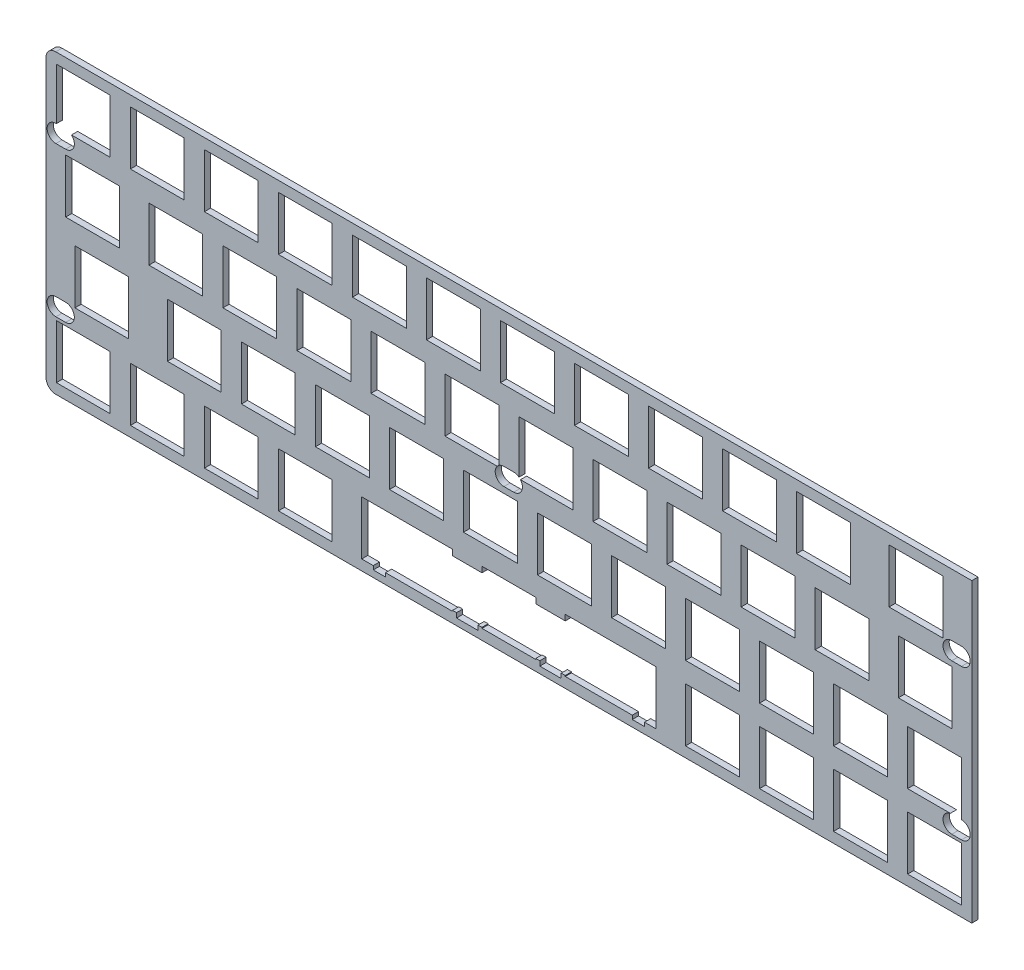
SolidWorks part; units mm, degrees
ref_plane "Front Plane" through (0, 0, 0) normal (0, 0, 1) x (1, 0, 0)
ref_plane "Top Plane" through (0, 0, 0) normal (0, 1, 0) x (1, 0, 0)
ref_plane "Right Plane" through (0, 0, 0) normal (1, 0, 0) x (0, 0, -1)
sketch "Model" plane through (0, 0, 0) normal (0, 0, 1) x (1, 0, 0)
  line L0 (0.0951, 76.4575) -> (238.37, 76.4575)
  line L1 (238.37, 76.4575) -> (238.37, 0.1075)
  line L2 (238.37, 0.1075) -> (0.0951, 0.1075)
  line L3 (0.0951, 0.1075) -> (0.0951, 76.4575)
  line L4 (81.3513, 16.6329) -> (81.3513, 2.7836)
  line L5 (81.3513, 2.7836) -> (84.3248, 2.7836)
  line L6 (84.3248, 2.7836) -> (84.3248, 1.8135)
  line L7 (84.3248, 1.8135) -> (87.4751, 1.8135)
  line L8 (87.4751, 1.8135) -> (87.4751, 2.7836)
  line L9 (87.4751, 2.7836) -> (104.725, 2.7836)
  line L10 (104.725, 2.7836) -> (104.725, 3.0138)
  line L11 (104.725, 3.0138) -> (105.756, 3.0138)
  line L12 (105.756, 3.0138) -> (105.756, 1.8135)
  line L13 (105.756, 1.8135) -> (111.275, 1.8135)
  line L14 (111.275, 1.8135) -> (111.275, 3.0138)
  line L15 (111.275, 3.0138) -> (112.306, 3.0138)
  line L16 (112.306, 3.0138) -> (112.306, 2.7836)
  line L17 (112.306, 2.7836) -> (126.157, 2.7836)
  line L18 (126.157, 2.7836) -> (126.157, 3.0138)
  line L19 (126.157, 3.0138) -> (127.187, 3.0138)
  line L20 (127.187, 3.0138) -> (127.187, 1.8135)
  line L21 (127.187, 1.8135) -> (132.707, 1.8135)
  line L22 (132.707, 1.8135) -> (132.707, 3.0138)
  line L23 (132.707, 3.0138) -> (133.737, 3.0138)
  line L24 (133.737, 3.0138) -> (133.737, 2.7836)
  line L25 (133.737, 2.7836) -> (150.987, 2.7836)
  line L26 (150.987, 2.7836) -> (150.987, 1.8135)
  line L27 (150.987, 1.8135) -> (154.138, 1.8135)
  line L28 (154.138, 1.8135) -> (154.138, 2.7836)
  line L29 (154.138, 2.7836) -> (157.113, 2.7836)
  line L30 (157.113, 2.7836) -> (157.113, 16.6329)
  line L31 (157.113, 16.6329) -> (133.737, 16.6329)
  line L32 (133.737, 16.6329) -> (133.737, 15.1639)
  line L33 (133.737, 15.1639) -> (126.157, 15.1639)
  line L34 (126.157, 15.1639) -> (126.157, 16.6329)
  line L35 (126.157, 16.6329) -> (112.306, 16.6329)
  line L36 (112.306, 16.6329) -> (112.306, 15.1639)
  line L37 (112.306, 15.1639) -> (104.725, 15.1639)
  line L38 (104.725, 15.1639) -> (104.725, 16.6329)
  line L39 (104.725, 16.6329) -> (81.3513, 16.6329)
  line L40 (221.845, 16.6329) -> (235.694, 16.6329)
  line L41 (235.694, 16.6329) -> (235.694, 2.7836)
  line L42 (235.694, 2.7836) -> (221.845, 2.7836)
  line L43 (221.845, 2.7836) -> (221.845, 16.6329)
  line L44 (202.795, 16.6329) -> (216.644, 16.6329)
  line L45 (216.644, 16.6329) -> (216.644, 2.7836)
  line L46 (216.644, 2.7836) -> (202.795, 2.7836)
  line L47 (202.795, 2.7836) -> (202.795, 16.6329)
  line L48 (183.745, 16.6329) -> (197.594, 16.6329)
  line L49 (197.594, 16.6329) -> (197.594, 2.7836)
  line L50 (197.594, 2.7836) -> (183.745, 2.7836)
  line L51 (183.745, 2.7836) -> (183.745, 16.6329)
  line L52 (164.695, 16.6329) -> (178.544, 16.6329)
  line L53 (178.544, 16.6329) -> (178.544, 2.7836)
  line L54 (178.544, 2.7836) -> (164.695, 2.7836)
  line L55 (164.695, 2.7836) -> (164.695, 16.6329)
  line L56 (59.92, 16.6329) -> (73.769, 16.6329)
  line L57 (73.769, 16.6329) -> (73.769, 2.7836)
  line L58 (73.769, 2.7836) -> (59.92, 2.7836)
  line L59 (59.92, 2.7836) -> (59.92, 16.6329)
  line L60 (40.87, 16.6329) -> (54.719, 16.6329)
  line L61 (54.719, 16.6329) -> (54.719, 2.7836)
  line L62 (54.719, 2.7836) -> (40.87, 2.7836)
  line L63 (40.87, 2.7836) -> (40.87, 16.6329)
  line L64 (21.8199, 16.6329) -> (35.669, 16.6329)
  line L65 (35.669, 16.6329) -> (35.669, 2.7836)
  line L66 (35.669, 2.7836) -> (21.8199, 2.7836)
  line L67 (21.8199, 2.7836) -> (21.8199, 16.6329)
  line L68 (2.7699, 16.6329) -> (16.6192, 16.6329)
  line L69 (16.6192, 16.6329) -> (16.6192, 2.7836)
  line L70 (16.6192, 2.7836) -> (2.7699, 2.7836)
  line L71 (2.7699, 2.7836) -> (2.7699, 16.6329)
  line L72 (221.845, 35.6828) -> (235.694, 35.6828)
  line L73 (235.694, 35.6828) -> (235.694, 21.8336)
  line L74 (235.694, 21.8336) -> (221.845, 21.8336)
  line L75 (221.845, 21.8336) -> (221.845, 35.6828)
  line L76 (202.795, 35.6828) -> (216.644, 35.6828)
  line L77 (216.644, 35.6828) -> (216.644, 21.8336)
  line L78 (216.644, 21.8336) -> (202.795, 21.8336)
  line L79 (202.795, 21.8336) -> (202.795, 35.6828)
  line L80 (183.745, 35.6828) -> (197.594, 35.6828)
  line L81 (197.594, 35.6828) -> (197.594, 21.8336)
  line L82 (197.594, 21.8336) -> (183.745, 21.8336)
  line L83 (183.745, 21.8336) -> (183.745, 35.6828)
  line L84 (164.695, 35.6828) -> (178.544, 35.6828)
  line L85 (178.544, 35.6828) -> (178.544, 21.8336)
  line L86 (178.544, 21.8336) -> (164.695, 21.8336)
  line L87 (164.695, 21.8336) -> (164.695, 35.6828)
  line L88 (145.644, 35.6828) -> (159.494, 35.6828)
  line L89 (159.494, 35.6828) -> (159.494, 21.8336)
  line L90 (159.494, 21.8336) -> (145.644, 21.8336)
  line L91 (145.644, 21.8336) -> (145.644, 35.6828)
  line L92 (126.594, 35.6828) -> (140.444, 35.6828)
  line L93 (140.444, 35.6828) -> (140.444, 21.8336)
  line L94 (140.444, 21.8336) -> (126.594, 21.8336)
  line L95 (126.594, 21.8336) -> (126.594, 35.6828)
  line L96 (107.544, 35.6828) -> (121.394, 35.6828)
  line L97 (121.394, 35.6828) -> (121.394, 21.8336)
  line L98 (121.394, 21.8336) -> (107.544, 21.8336)
  line L99 (107.544, 21.8336) -> (107.544, 35.6828)
  line L100 (88.4936, 35.6828) -> (102.344, 35.6828)
  line L101 (102.344, 35.6828) -> (102.344, 21.8336)
  line L102 (102.344, 21.8336) -> (88.4936, 21.8336)
  line L103 (88.4936, 21.8336) -> (88.4936, 35.6828)
  line L104 (69.445, 35.6828) -> (83.294, 35.6828)
  line L105 (83.294, 35.6828) -> (83.294, 21.8336)
  line L106 (83.294, 21.8336) -> (69.445, 21.8336)
  line L107 (69.445, 21.8336) -> (69.445, 35.6828)
  line L108 (50.395, 35.6828) -> (64.244, 35.6828)
  line L109 (64.244, 35.6828) -> (64.244, 21.8336)
  line L110 (64.244, 21.8336) -> (50.395, 21.8336)
  line L111 (50.395, 21.8336) -> (50.395, 35.6828)
  line L112 (31.3449, 35.6828) -> (45.194, 35.6828)
  line L113 (45.194, 35.6828) -> (45.194, 21.8336)
  line L114 (45.194, 21.8336) -> (31.3449, 21.8336)
  line L115 (31.3449, 21.8336) -> (31.3449, 35.6828)
  line L116 (7.531, 35.6828) -> (21.3817, 35.6828)
  line L117 (21.3817, 35.6828) -> (21.3817, 21.8336)
  line L118 (21.3817, 21.8336) -> (7.531, 21.8336)
  line L119 (7.531, 21.8336) -> (7.531, 35.6828)
  line L120 (219.462, 54.7328) -> (233.313, 54.7328)
  line L121 (233.313, 54.7328) -> (233.313, 40.8838)
  line L122 (233.313, 40.8838) -> (219.462, 40.8838)
  line L123 (219.462, 40.8838) -> (219.462, 54.7328)
  line L124 (198.031, 54.7328) -> (211.882, 54.7328)
  line L125 (211.882, 54.7328) -> (211.882, 40.8838)
  line L126 (211.882, 40.8838) -> (198.031, 40.8838)
  line L127 (198.031, 40.8838) -> (198.031, 54.7328)
  line L128 (178.981, 54.7328) -> (192.832, 54.7328)
  line L129 (192.832, 54.7328) -> (192.832, 40.8838)
  line L130 (192.832, 40.8838) -> (178.981, 40.8838)
  line L131 (178.981, 40.8838) -> (178.981, 54.7328)
  line L132 (159.931, 54.7328) -> (173.782, 54.7328)
  line L133 (173.782, 54.7328) -> (173.782, 40.8838)
  line L134 (173.782, 40.8838) -> (159.931, 40.8838)
  line L135 (159.931, 40.8838) -> (159.931, 54.7328)
  line L136 (140.881, 54.7328) -> (154.732, 54.7328)
  line L137 (154.732, 54.7328) -> (154.732, 40.8838)
  line L138 (154.732, 40.8838) -> (140.881, 40.8838)
  line L139 (140.881, 40.8838) -> (140.881, 54.7328)
  line L140 (121.831, 54.7328) -> (135.682, 54.7328)
  line L141 (135.682, 54.7328) -> (135.682, 40.8838)
  line L142 (135.682, 40.8838) -> (121.831, 40.8838)
  line L143 (121.831, 40.8838) -> (121.831, 54.7328)
  line L144 (102.781, 54.7328) -> (116.632, 54.7328)
  line L145 (116.632, 54.7328) -> (116.632, 40.8838)
  line L146 (116.632, 40.8838) -> (102.781, 40.8838)
  line L147 (102.781, 40.8838) -> (102.781, 54.7328)
  line L148 (83.7311, 54.7328) -> (97.5815, 54.7328)
  line L149 (97.5815, 54.7328) -> (97.5815, 40.8838)
  line L150 (97.5815, 40.8838) -> (83.7311, 40.8838)
  line L151 (83.7311, 40.8838) -> (83.7311, 54.7328)
  line L152 (64.6811, 54.7328) -> (78.5315, 54.7328)
  line L153 (78.5315, 54.7328) -> (78.5315, 40.8838)
  line L154 (78.5315, 40.8838) -> (64.6811, 40.8838)
  line L155 (64.6811, 40.8838) -> (64.6811, 54.7328)
  line L156 (45.6311, 54.7328) -> (59.4815, 54.7328)
  line L157 (59.4815, 54.7328) -> (59.4815, 40.8838)
  line L158 (59.4815, 40.8838) -> (45.6311, 40.8838)
  line L159 (45.6311, 40.8838) -> (45.6311, 54.7328)
  line L160 (26.581, 54.7328) -> (40.4315, 54.7328)
  line L161 (40.4315, 54.7328) -> (40.4315, 40.8838)
  line L162 (40.4315, 40.8838) -> (26.581, 40.8838)
  line L163 (26.581, 40.8838) -> (26.581, 54.7328)
  line L164 (5.1511, 54.7328) -> (19.0004, 54.7328)
  line L165 (19.0004, 54.7328) -> (19.0004, 40.8838)
  line L166 (19.0004, 40.8838) -> (5.1511, 40.8838)
  line L167 (5.1511, 40.8838) -> (5.1511, 54.7328)
  line L168 (217.081, 73.7828) -> (230.932, 73.7828)
  line L169 (230.932, 73.7828) -> (230.932, 59.9338)
  line L170 (230.932, 59.9338) -> (217.081, 59.9338)
  line L171 (217.081, 59.9338) -> (217.081, 73.7828)
  line L172 (193.27, 73.7828) -> (207.119, 73.7828)
  line L173 (207.119, 73.7828) -> (207.119, 59.9338)
  line L174 (207.119, 59.9338) -> (193.27, 59.9338)
  line L175 (193.27, 59.9338) -> (193.27, 73.7828)
  line L176 (174.22, 73.7828) -> (188.069, 73.7828)
  line L177 (188.069, 73.7828) -> (188.069, 59.9338)
  line L178 (188.069, 59.9338) -> (174.22, 59.9338)
  line L179 (174.22, 59.9338) -> (174.22, 73.7828)
  line L180 (155.17, 73.7828) -> (169.019, 73.7828)
  line L181 (169.019, 73.7828) -> (169.019, 59.9338)
  line L182 (169.019, 59.9338) -> (155.17, 59.9338)
  line L183 (155.17, 59.9338) -> (155.17, 73.7828)
  line L184 (136.12, 73.7828) -> (149.969, 73.7828)
  line L185 (149.969, 73.7828) -> (149.969, 59.9338)
  line L186 (149.969, 59.9338) -> (136.12, 59.9338)
  line L187 (136.12, 59.9338) -> (136.12, 73.7828)
  line L188 (117.07, 73.7828) -> (130.919, 73.7828)
  line L189 (130.919, 73.7828) -> (130.919, 59.9338)
  line L190 (130.919, 59.9338) -> (117.07, 59.9338)
  line L191 (117.07, 59.9338) -> (117.07, 73.7828)
  line L192 (98.02, 73.7828) -> (111.869, 73.7828)
  line L193 (111.869, 73.7828) -> (111.869, 59.9338)
  line L194 (111.869, 59.9338) -> (98.02, 59.9338)
  line L195 (98.02, 59.9338) -> (98.02, 73.7828)
  line L196 (78.97, 73.7828) -> (92.819, 73.7828)
  line L197 (92.819, 73.7828) -> (92.819, 59.9338)
  line L198 (92.819, 59.9338) -> (78.97, 59.9338)
  line L199 (78.97, 59.9338) -> (78.97, 73.7828)
  line L200 (59.92, 73.7828) -> (73.769, 73.7828)
  line L201 (73.769, 73.7828) -> (73.769, 59.9338)
  line L202 (73.769, 59.9338) -> (59.92, 59.9338)
  line L203 (59.92, 59.9338) -> (59.92, 73.7828)
  line L204 (40.87, 73.7828) -> (54.719, 73.7828)
  line L205 (54.719, 73.7828) -> (54.719, 59.9338)
  line L206 (54.719, 59.9338) -> (40.87, 59.9338)
  line L207 (40.87, 59.9338) -> (40.87, 73.7828)
  line L208 (21.8199, 73.7828) -> (35.669, 73.7828)
  line L209 (35.669, 73.7828) -> (35.669, 59.9338)
  line L210 (35.669, 59.9338) -> (21.8199, 59.9338)
  line L211 (21.8199, 59.9338) -> (21.8199, 73.7828)
  line L212 (2.7699, 73.7828) -> (16.6192, 73.7828)
  line L213 (16.6192, 73.7828) -> (16.6192, 59.9338)
  line L214 (16.6192, 59.9338) -> (2.7699, 59.9338)
  line L215 (2.7699, 59.9338) -> (2.7699, 73.7828)
extrude "Boss-Extrude1" add sketch "Model" along normal blind 1.6
fillet "Fillet1" radius 2.5 2 edges at (0.0951, 0.1075, 0.8) (0.0951, 76.4575, 0.8)
sketch "Sketch10" plane through (0, 0, 1.6) normal (0, 0, 1) x (1, 0, 0)
  line L0 (233.2257, 20.8643) -> (235.7275, 20.8468) construction
  line L1 (235.71, 18.3475) -> (233.2287, 18.3649) construction
  line L2 (2.5951, 0.1075) -> (238.37, 0.1075) construction
  line L3 (238.37, 0.1075) -> (238.37, 76.4575) construction
  line L4 (235.71, 57.0181) -> (233.2081, 57.0181) construction
  line L5 (233.2081, 59.5175) -> (235.71, 59.5175) construction
  line L6 (238.37, 76.4575) -> (2.5951, 76.4575) construction
  line L7 (120.46, 38.2181) -> (117.9581, 38.2181) construction
  line L8 (117.9581, 40.7175) -> (120.46, 40.7175) construction
  line L9 (5.137, 57.0181) -> (2.6351, 57.0181) construction
  line L10 (2.6351, 59.5175) -> (5.137, 59.5175) construction
  line L11 (5.137, 18.4075) -> (2.6351, 18.4075) construction
  line L12 (2.6351, 20.9068) -> (5.137, 20.9068) construction
  line L14 (0.0951, 73.9575) -> (0.0951, 2.6075) construction
  line L26 (2.6351, 60.5175) -> (5.137, 60.5175)
  line L27 (5.137, 56.0181) -> (2.6351, 56.0181)
  line L28 (2.6351, 21.9068) -> (5.137, 21.9068)
  line L29 (5.137, 17.4075) -> (2.6351, 17.4075)
  line L30 (117.9581, 41.7175) -> (120.46, 41.7175)
  line L31 (120.46, 37.2181) -> (117.9581, 37.2181)
  line L32 (233.2081, 60.5175) -> (235.71, 60.5175)
  line L33 (235.71, 56.0181) -> (233.2081, 56.0181)
  line L34 (235.703, 17.3475) -> (233.2252, 17.3649)
  line L35 (233.2292, 21.8643) -> (235.7345, 21.8468)
  arc A0 (235.71, 18.3475) -> (235.7275, 20.8468) centre (235.7188, 19.5971) ccw construction
  arc A1 (233.2257, 20.8643) -> (233.2287, 18.3649) centre (233.2272, 19.6146) ccw construction
  arc A2 (235.71, 57.0181) -> (235.71, 59.5175) centre (235.71, 58.2678) ccw construction
  arc A3 (233.2081, 59.5175) -> (233.2081, 57.0181) centre (233.2081, 58.2678) ccw construction
  arc A4 (120.46, 38.2181) -> (120.46, 40.7175) centre (120.46, 39.4678) ccw construction
  arc A5 (117.9581, 40.7175) -> (117.9581, 38.2181) centre (117.9581, 39.4678) ccw construction
  arc A6 (5.137, 57.0181) -> (5.137, 59.5175) centre (5.137, 58.2678) ccw construction
  arc A7 (2.6351, 59.5175) -> (2.6351, 57.0181) centre (2.6351, 58.2678) ccw construction
  arc A8 (5.137, 18.4075) -> (5.137, 20.9068) centre (5.137, 19.6572) ccw construction
  arc A9 (2.6351, 20.9068) -> (2.6351, 18.4075) centre (2.6351, 19.6572) ccw construction
  arc A22 (5.137, 56.0181) -> (5.137, 60.5175) centre (5.137, 58.2678) ccw
  arc A23 (2.6351, 60.5175) -> (2.6351, 56.0181) centre (2.6351, 58.2678) ccw
  arc A24 (5.137, 17.4075) -> (5.137, 21.9068) centre (5.137, 19.6572) ccw
  arc A25 (2.6351, 21.9068) -> (2.6351, 17.4075) centre (2.6351, 19.6572) ccw
  arc A26 (120.46, 37.2181) -> (120.46, 41.7175) centre (120.46, 39.4678) ccw
  arc A27 (117.9581, 41.7175) -> (117.9581, 37.2181) centre (117.9581, 39.4678) ccw
  arc A28 (235.71, 56.0181) -> (235.71, 60.5175) centre (235.71, 58.2678) ccw
  arc A29 (233.2081, 60.5175) -> (233.2081, 56.0181) centre (233.2081, 58.2678) ccw
  arc A30 (233.2292, 21.8643) -> (233.2252, 17.3649) centre (233.2272, 19.6146) ccw
  arc A31 (235.703, 17.3475) -> (235.7345, 21.8468) centre (235.7188, 19.5971) ccw
  dimension "D13" = 1.2497
  dimension "D14" = 1.2497
  dimension "D1" = 2.5019
  dimension "D2" = 1.2497
  dimension "D3" = 1.2497
  dimension "D4" = 2.4994
  dimension "D5" = 18.24
  dimension "D6" = 2.66
  dimension "D7" = 1.2497
  dimension "D8" = 1.2497
  dimension "D9" = 2.5019
  dimension "D10" = 2.4994
  dimension "D11" = 16.94
  dimension "D12" = 2.66
  dimension "D15" = 117.91
  dimension "D16" = 35.74
  dimension "D17" = 18.3
  dimension "D18" = 2.54
  dimension "D19" = 16.94
  dimension "D20" = 2.54
  dimension "D22" = 1
  dimension "D23" = 1
  dimension "D24" = 1
  dimension "D25" = 1
  dimension "D26" = 1
extrude "Cut-Extrude1" cut sketch "Sketch10" against normal blind 1.6
